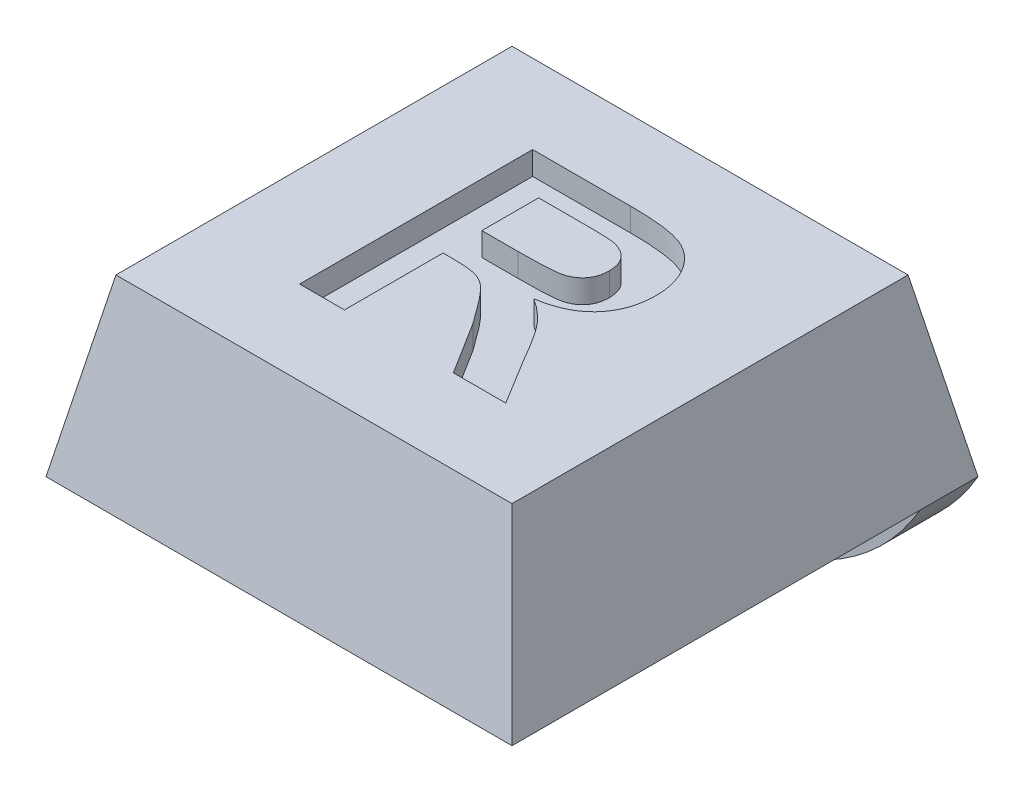
SolidWorks part; units mm, degrees
ref_plane "Front Plane" through (0, 0, 0) normal (0, 0, 1) x (1, 0, 0)
ref_plane "Top Plane" through (0, 0, 0) normal (0, 1, 0) x (1, 0, 0)
ref_plane "Right Plane" through (0, 0, 0) normal (1, 0, 0) x (0, 0, -1)
sketch "Sketch1" plane through (0, 0, 0) normal (0, 1, 0) x (1, 0, 0)
  line L1 (0, 0) -> (8, 0)
  line L2 (0, 0) -> (0, 8)
  line L3 (0, 8) -> (8, 8)
  line L4 (8, 0) -> (8, 8)
  dimension "D1" = 8
  dimension "D2" = 8
extrude "Boss-Extrude1" add sketch "Sketch1" along normal blind 3
sketch "Sketch2" plane through (0, 0, 0) normal (0, 0, 1) x (1, 0, 0)
  line L0 (0, 0) -> (0.6, 3)
  line L1 (0, 3) -> (8, 3) construction
  line L2 (0.6, 3) -> (0, 3)
  line L3 (0, 3) -> (0, 0)
  line L4 (8, 0) -> (7.4, 3)
  line L5 (7.4, 3) -> (8, 3)
  line L6 (8, 3) -> (8, 0)
  dimension "D1" = 0.6
  dimension "D2" = 0.6
extrude "Cut-Extrude1" cut sketch "Sketch2" against normal through all both and the other way through all
sketch "Sketch3" plane through (0, 0, 0) normal (1, 0, 0) x (0, 0, -1)
  line L0 (0, 0) -> (0.6, 3)
  line L1 (8, 3) -> (0, 3) construction
  line L2 (0.6, 3) -> (0, 3)
  line L3 (0, 3) -> (0, 0)
  line L4 (8, 3) -> (7.4, 3)
  line L5 (7.4, 3) -> (8, 0)
  line L6 (8, 3) -> (8, 0)
  dimension "D1" = 0.6
  dimension "D2" = 0.6
extrude "Cut-Extrude2" cut sketch "Sketch3" along normal blind 11
sketch "Sketch4" plane through (0, 0, 0) normal (0, -1, 0) x (1, 0, 0)
  line L0 (8, 0) -> (8, -8) construction
  line L3 (0, 0) -> (8, 0) construction
  circle A0 centre (4, -3.75) radius 1.8
  dimension "D1" = 3.6
  dimension "D2" = 4
  dimension "D3" = 3.75
extrude "Cut-Extrude3" cut sketch "Sketch4" against normal blind 0.8
sketch "Sketch5" plane through (0, 0, 0) normal (0, -1, 0) x (1, 0, 0)
  line L0 (8, 0) -> (8, -8) construction
  line L1 (0, -8) -> (8, -8)
  line L2 (0, -8) -> (0, -7)
  line L3 (0, -7) -> (8, -7)
  line L4 (8, -8) -> (8, -7)
  dimension "D1" = 1
extrude "Boss-Extrude2" add sketch "Sketch5" along normal blind 2
fillet "Fillet1" radius 4 2 edges at (8, -2, -7.5) (0, -2, -7.5)
sketch "Sketch6" plane through (0, 3, 0) normal (0, 1, 0) x (1, 0, 0)
  text T0 "R" font "Arial" height 4
extrude "Cut-Extrude4" cut sketch "Sketch6" against normal blind 0.4
